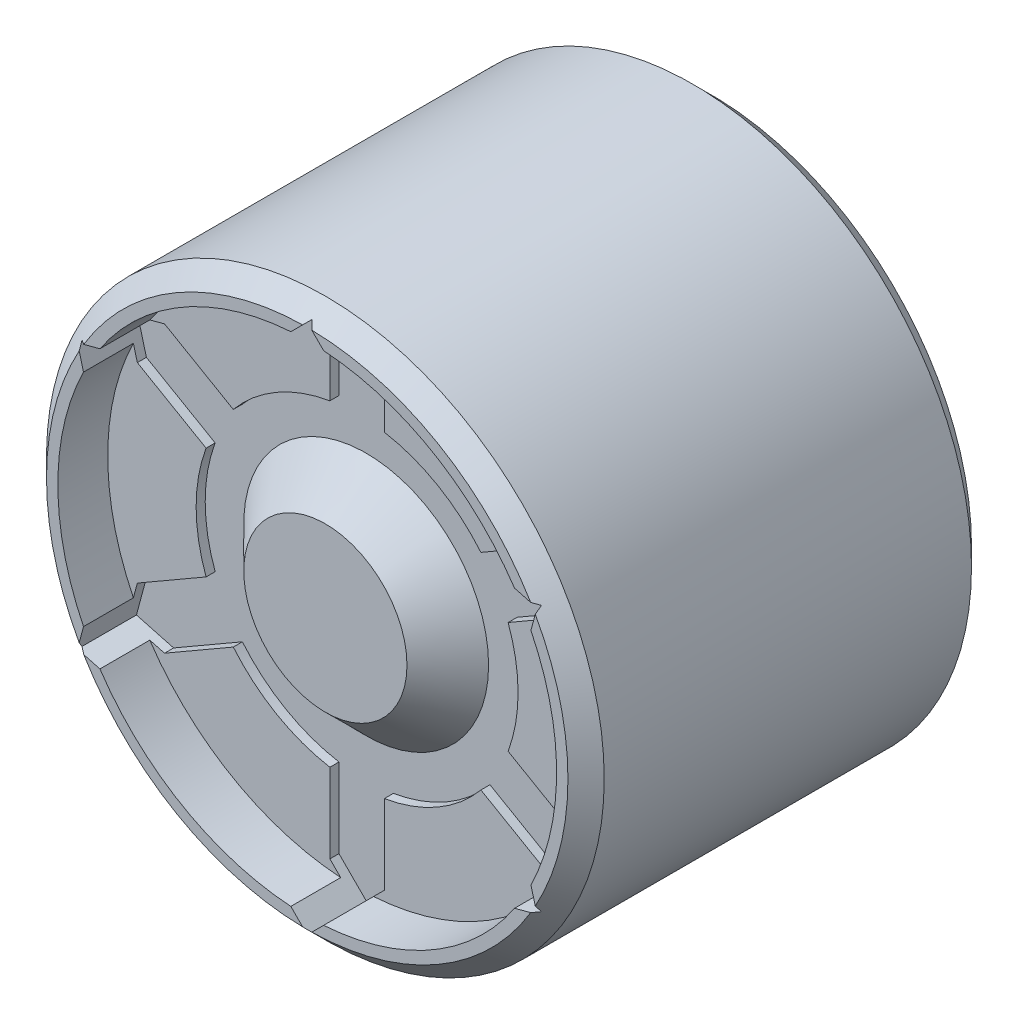
SolidWorks part; units mm, degrees
ref_plane "정면" through (0, 0, 0) normal (0, 0, 1) x (1, 0, 0)
ref_plane "윗면" through (0, 0, 0) normal (0, 1, 0) x (1, 0, 0)
ref_plane "우측면" through (0, 0, 0) normal (1, 0, 0) x (0, 0, -1)
sketch "스케치1" plane through (0, 0, 0) normal (0, 0, 1) x (1, 0, 0)
  line L0 (0, 0) -> (0, 5.85) construction
  line L1 (0, 5.85) -> (-0.6, 5.25)
  line L2 (-0.6, 5.25) -> (-0.6, 1.6705)
  line L3 (0.6, 5.25) -> (0.6, 1.6705)
  line L4 (0, 5.85) -> (0.6, 5.25)
  line L5 (4.2466, 3.1446) -> (1.1467, 1.3549)
  line L6 (5.0662, 2.925) -> (4.2466, 3.1446)
  line L7 (5.0662, 2.925) -> (4.8466, 2.1054)
  line L8 (4.8466, 2.1054) -> (1.7467, 0.3156)
  line L9 (4.8466, -2.1054) -> (1.7467, -0.3156)
  line L10 (5.0662, -2.925) -> (4.8466, -2.1054)
  line L11 (5.0662, -2.925) -> (4.2466, -3.1446)
  line L12 (4.2466, -3.1446) -> (1.1467, -1.3549)
  line L13 (0.6, -5.25) -> (0.6, -1.6705)
  line L14 (0, -5.85) -> (0.6, -5.25)
  line L15 (0, -5.85) -> (-0.6, -5.25)
  line L16 (-0.6, -5.25) -> (-0.6, -1.6705)
  line L17 (-4.2466, -3.1446) -> (-1.1467, -1.3549)
  line L18 (-5.0662, -2.925) -> (-4.2466, -3.1446)
  line L19 (-5.0662, -2.925) -> (-4.8466, -2.1054)
  line L20 (-4.8466, -2.1054) -> (-1.7467, -0.3156)
  line L21 (-4.8466, 2.1054) -> (-1.7467, 0.3156)
  line L22 (-5.0662, 2.925) -> (-4.8466, 2.1054)
  line L23 (-5.0662, 2.925) -> (-4.2466, 3.1446)
  line L24 (-4.2466, 3.1446) -> (-1.1467, 1.3549)
  circle A0 centre (0, 0) radius 1.775
  circle A1 centre (0, 0) radius 6.15
  point P36 (0, 0)
  dimension "D1" = 1.2
  dimension "D2" = 3.55
  dimension "D3" = 12.3
  dimension "D4" = 90
  dimension "D5" = 5.85
  dimension "D6" = 6
extrude "보스-돌출1" add sketch "스케치1" along normal blind 0.2 contours A1 A0 L5 L6 L7 L8 L9 L10 L11 L12 L13 L14 L15 L16 L17 L18 L19 L20 L21 L22 L23 L24 L2 L1 L4 L3 region at (-5.9761, 0, 0)
sketch "스케치2" plane through (0, 0, 0) normal (0, 0, 1) x (1, 0, 0)
  circle A0 centre (0, 0) radius 2.8
  dimension "D1" = 5.6
extrude "보스-돌출2" add sketch "스케치2" along normal blind 0.9 separate body
sketch "스케치3" plane through (0, 0, 0.2) normal (0, 0, 1) x (1, 0, 0)
  line L0 (-4.9338, -2.4306) -> (-5.0662, -2.925)
  line L1 (-5.0662, -2.925) -> (-4.8466, -2.1054) construction
  line L2 (-5.0662, -2.925) -> (-4.5719, -3.0575)
  line L3 (-5.0662, -2.925) -> (-4.2466, -3.1446) construction
  line L4 (-4.5719, 3.0575) -> (-5.0662, 2.925)
  line L5 (-5.0662, 2.925) -> (-4.9338, 2.4306)
  line L6 (0.3619, 5.4881) -> (0, 5.85)
  line L7 (0, 5.85) -> (-0.3619, 5.4881)
  line L8 (4.9338, 2.4306) -> (5.0662, 2.925)
  line L9 (5.0662, 2.925) -> (4.5719, 3.0575)
  line L10 (4.5719, -3.0575) -> (5.0662, -2.925)
  line L11 (5.0662, -2.925) -> (4.9338, -2.4306)
  line L12 (-0.3619, -5.4881) -> (0, -5.85)
  line L13 (0, -5.85) -> (0.3619, -5.4881)
  arc A0 (-4.5719, -3.0575) -> (-0.3619, -5.4881) centre (0, 0) ccw
  circle A1 centre (0, 0) radius 6.15
  circle A2 centre (0, 0) radius 6.15 construction
  arc A3 (0.3619, -5.4881) -> (4.5719, -3.0575) centre (0, 0) ccw
  arc A4 (4.9338, -2.4306) -> (4.9338, 2.4306) centre (0, 0) ccw
  arc A5 (4.5719, 3.0575) -> (0.3619, 5.4881) centre (0, 0) ccw
  arc A6 (-0.3619, 5.4881) -> (-4.5719, 3.0575) centre (0, 0) ccw
  arc A7 (-4.9338, 2.4306) -> (-4.9338, -2.4306) centre (0, 0) ccw
  point P33 (0, 0)
  dimension "D1" = 11
  dimension "D2" = 6
extrude "보스-돌출3" add sketch "스케치3" along normal blind 1.1
sketch "스케치4" plane through (0, 0, 0) normal (0, 0, 1) x (1, 0, 0)
  circle A0 centre (0, 0) radius 6.15
  circle A1 centre (0, 0) radius 6.15 construction
extrude "보스-돌출4" add sketch "스케치4" against normal blind 0.6
sketch "스케치6" plane through (0, 0, 0.2) normal (0, 0, 1) x (1, 0, 0)
  line L0 (0, 0) -> (0, 3.55) construction
  circle A0 centre (0, 0) radius 3.55
  circle A1 centre (0, 0) radius 2.8
  circle A2 centre (0, 0) radius 2.8 construction
  dimension "D1" = 3.55
extrude "컷-돌출2" cut sketch "스케치6" against normal blind 0.2
sketch "스케치7" plane through (0, 0, -0.6) normal (0, 0, -1) x (-1, 0, 0)
  circle A0 centre (0, 0) radius 6.15
  circle A1 centre (0, 0) radius 4.75
  circle A2 centre (0, 0) radius 6.15 construction
  dimension "D2" = 9.5
extrude "보스-돌출5" add sketch "스케치7" along normal blind 7
chamfer "모따기4" distance 2.5 angle 45 1 edges at (-4.75, 0, -0.6)
chamfer "모따기5" distance 0.4 angle 45 1 edges at (6.15, 0, 1.3)
chamfer "모따기6" distance 0.4 angle 45 1 edges at (-6.15, 0, -7.6)
chamfer "모따기7" distance 1 angle 45 1 edges at (2.8, 0, 0.9)
chamfer "모따기8" distance 0.3 angle 45 1 edges at (-4.75, 0, -7.6)
